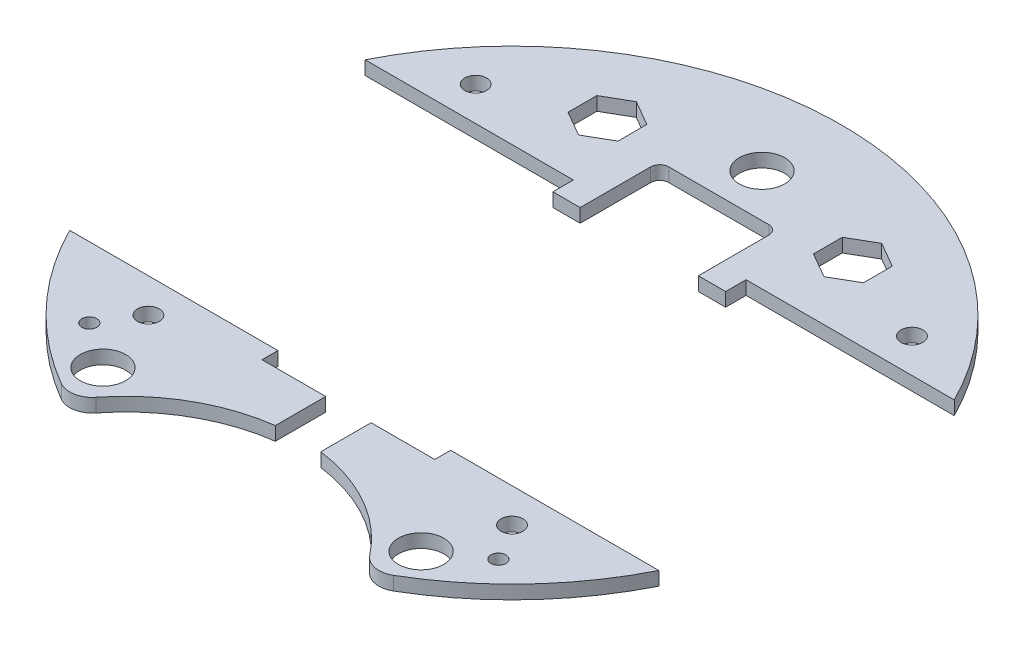
SolidWorks part; units mm, degrees
material "Acrylic (Medium-high impact)"
ref_plane "Front Plane" through (0, 0, 0) normal (0, 0, 1) x (1, 0, 0)
ref_plane "Top Plane" through (0, 0, 0) normal (0, 1, 0) x (1, 0, 0)
ref_plane "Right Plane" through (0, 0, 0) normal (1, 0, 0) x (0, 0, -1)
sketch "Sketch1" plane through (0, 0, 0) normal (0, 1, 0) x (1, 0, 0)
  line L0 (0, -85) -> (-32.4891, -64.8129) construction
  line L1 (0, -85) -> (0, 0) construction
  arc A0 (36.5434, -62.6165) -> (-36.5434, -62.6165) centre (0, 0) ccw
  arc A1 (30.0898, -61.3851) -> (-30.0898, -61.3851) centre (0, -85) ccw
  arc A2 (36.5434, -62.6165) -> (30.0898, -61.3851) centre (34.0231, -58.2982) cw
  arc A3 (-30.0898, -61.3851) -> (-36.5434, -62.6165) centre (-34.0231, -58.2982) cw
  dimension "D1" = 145
  dimension "D2" = 76.5
  dimension "D4" = 5
  dimension "D3" = 85
extrude "Boss-Extrude1" add sketch "Sketch1" along normal blind 3
sketch "solenoid placement" plane through (0, 3, 0) normal (0, 1, 0) x (1, 0, 0)
  line L4 (-19, -36) -> (19, -36)
  line L5 (-19, 28) -> (-19, -36)
  line L6 (19, 28) -> (-19, 28)
  line L7 (19, -36) -> (19, 28)
  line L8 (-19, -36) -> (19, -36)
  line L9 (-19, 28) -> (-19, -36)
  line L10 (19, 28) -> (-19, 28)
  line L11 (19, -36) -> (19, 28)
  dimension "D1" = 0
extrude "Cut-Extrude1" cut sketch "solenoid placement" against normal through all
sketch "Sketch4" plane through (0, 3, 0) normal (0, 1, 0) x (1, 0, 0)
  line L6 (19, 28) -> (-19, 28) construction
  line L10 (-13, 28) -> (13, 28)
  line L11 (13, 28) -> (13, 43.5)
  line L12 (11, 45.5) -> (-11, 45.5)
  line L13 (-13, 43.5) -> (-13, 28)
  arc A5 (13, 43.5) -> (11, 45.5) centre (11, 43.5) ccw
  arc A7 (-11, 45.5) -> (-13, 43.5) centre (-11, 43.5) ccw
  point P10 (0, 28)
  point P11 (0, 28)
  dimension "D3" = 2
  dimension "D1" = 26
  dimension "D2" = 17.5
extrude "Cut-Extrude4" cut sketch "Sketch4" against normal through all
sketch "Sketch5" plane through (0, 3, 0) normal (0, 1, 0) x (1, 0, 0)
  line L6 (0, 0) -> (0, 72.5) construction
  line L7 (-21.5, 51.1754) -> (-27, 54.3509)
  line L8 (-27, 54.3509) -> (-32.5, 51.1754)
  line L9 (-32.5, 51.1754) -> (-32.5, 44.8246)
  line L10 (-32.5, 44.8246) -> (-27, 41.6491)
  line L11 (-27, 41.6491) -> (-21.5, 44.8246)
  line L12 (-21.5, 44.8246) -> (-21.5, 51.1754)
  line L13 (21.5, 44.8246) -> (21.5, 51.1754)
  line L14 (27, 41.6491) -> (21.5, 44.8246)
  line L15 (32.5, 44.8246) -> (27, 41.6491)
  line L16 (32.5, 51.1754) -> (32.5, 44.8246)
  line L17 (27, 54.3509) -> (32.5, 51.1754)
  line L18 (21.5, 51.1754) -> (27, 54.3509)
  circle A0 centre (-27, 48) radius 5.5 construction
  arc A1 (36.5434, -62.6165) -> (-36.5434, -62.6165) centre (0, 0) ccw construction
  circle A2 centre (27, 48) radius 5.5 construction
  dimension "D1" = 11
extrude "Cut-Extrude5" cut sketch "Sketch5" against normal through all
sketch "Sketch6" plane through (0, 3, 0) normal (0, 1, 0) x (1, 0, 0)
  circle A1 centre (40, -40) radius 2.4
  circle A2 centre (40, -40) radius 2.4
  circle A3 centre (-40, -40) radius 2.4
  circle A4 centre (-40, -40) radius 2.4
  circle A5 centre (48, 40) radius 2.4
  circle A6 centre (48, 40) radius 2.4
  circle A7 centre (-48, 40) radius 2.4
  circle A8 centre (-48, 40) radius 2.4
  dimension "D1" = 0
  dimension "D2" = 0
  dimension "D3" = 0
  dimension "D4" = 0
extrude "Cut-Extrude6" cut sketch "Sketch6" against normal through all
sketch "Sketch3" plane through (0, 3, 0) normal (0, 1, 0) x (1, 0, 0)
  line L0 (-19, 28) -> (-19, 32.5)
  line L1 (72.5, -32.5) -> (-72.5, -32.5)
  line L2 (72.5, -32.5) -> (72.5, 32.5)
  line L3 (72.5, 32.5) -> (19, 32.5)
  line L4 (-72.5, -32.5) -> (-72.5, 32.5)
  line L5 (72.5, -32.5) -> (-72.5, 32.5) construction
  line L6 (72.5, 32.5) -> (-72.5, -32.5) construction
  line L7 (-19, 28) -> (19, 28)
  line L8 (19, 28) -> (19, 32.5)
  line L9 (-19, 32.5) -> (-72.5, 32.5)
  arc A0 (36.5434, -62.6165) -> (-36.5434, -62.6165) centre (0, 0) ccw construction
  point P0 (0, 0)
  dimension "D1" = 65
extrude "Cut-Extrude3" cut sketch "Sketch3" against normal through all
sketch "Sketch7" plane through (0, 3, 0) normal (0, 1, 0) x (1, 0, 0)
  line L5 (-5, 0) -> (5, 0)
  line L6 (-5, 0) -> (-5, -50)
  line L7 (-5, -50) -> (5, -50)
  line L8 (5, 0) -> (5, -50)
  point P4 (0, 0)
  dimension "D1" = 10
  dimension "D2" = 50
extrude "Cut-Extrude7" cut sketch "Sketch7" against normal through all
sketch "Sketch9" plane through (0, 3, 0) normal (0, -1, 0) x (1, 0, 0)
  circle A1 centre (35, 55) radius 5
  circle A2 centre (35, 55) radius 5
  circle A3 centre (-35, 55) radius 5
  circle A4 centre (-35, 55) radius 5
  dimension "D1" = 0
  dimension "D2" = 0
extrude "Cut-Extrude11" cut sketch "Sketch9" along normal through all
sketch "Sketch10" plane through (0, 3, 0) normal (0, 1, 0) x (1, 0, 0)
  circle A1 centre (0, 55) radius 5
  circle A2 centre (0, 55) radius 5
  dimension "D1" = 0
extrude "Cut-Extrude12" cut sketch "Sketch10" against normal through all and the other way through all
sketch "Sketch11" plane through (0, 3, 0) normal (0, 1, 0) x (1, 0, 0)
  line L0 (0, 0) -> (0, -22.1714) construction
  circle A0 centre (45, -48) radius 1.65
  circle A1 centre (-45, -48) radius 1.65
  dimension "D3" = 3.3
  dimension "D1" = 45
  dimension "D2" = 48
extrude "Cut-Extrude13" cut sketch "Sketch11" against normal through all
equation "\"smallPulleyTeeth\"= 30"
equation "\"largePulleyTeeth\"= 30"
equation "\"eighthThick\"= 3.0mm"
equation "\"sixteenthThick\" = 1.7mm"
equation "\"quarterThick\"=6.0mm"
equation "\"OD\" = 145mm"
equation "\"puckAngle\" = 60.5deg"
equation "\"D1@Sketch1\"=\"OD\""
equation "\"puckDiam\" = 76.5mm"
equation "\"D2@Sketch1\"=\"puckDiam\""
equation "\"D1@Boss-Extrude1\"=\"eighthThick\""
equation "\"axlePress\" = 5.9mm"
equation "\"press\" = 0.2mm"
equation "\"wheelClear\" = 0.3mm"
equation "\"10-32clear\" = 4.8mm"
equation "\"6-32clear\" = 3.3mm"
equation "\"8-32clear\" = 4.0mm"
equation "\"wheelHeight\" = 22mm"
equation "\"wheelWell\" = 65mm"
equation "\"D1@Sketch3\"=\"wheelWell\""
equation "\"puckDist\" = 85mm"
equation "\"scoopFillet\" = 5mm"
equation "\"4-40clear\" = 3.0mm"
equation "\"D3@Sketch1\"=\"puckDist\""
equation "\"D4@Sketch1\"=\"scoopFillet\""
equation "\"D3@Sketch11\"=\"6-32clear\""
